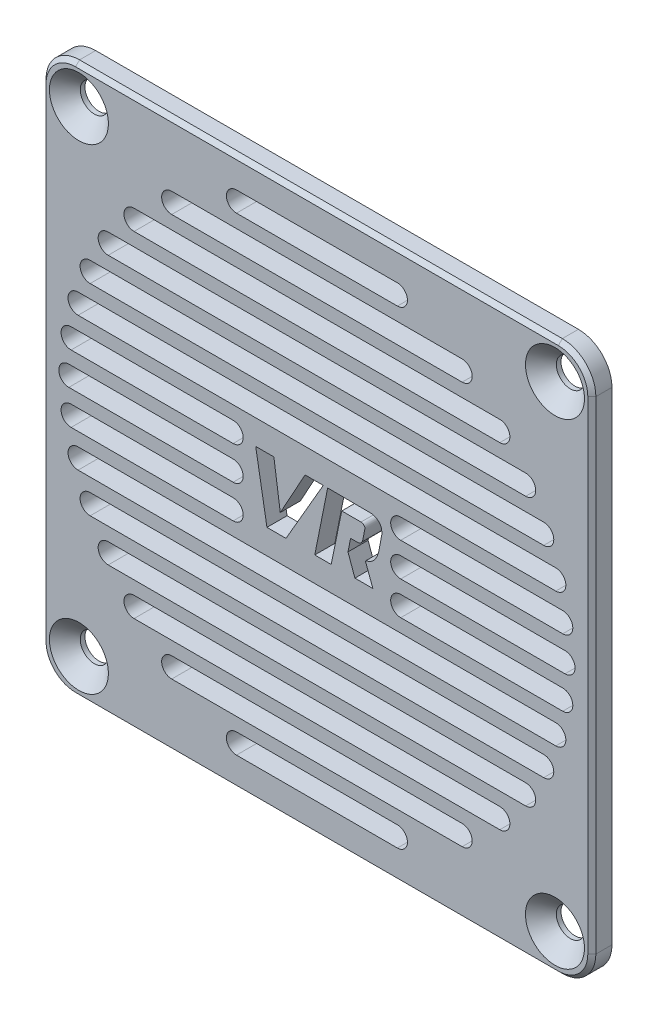
SolidWorks part; units mm, degrees
ref_plane "Front Plane" through (0, 0, 0) normal (0, 0, 1) x (1, 0, 0)
ref_plane "Top Plane" through (0, 0, 0) normal (0, 1, 0) x (1, 0, 0)
ref_plane "Right Plane" through (0, 0, 0) normal (1, 0, 0) x (0, 0, -1)
sketch "Sketch1" plane through (0, 0, 0) normal (0, 0, 1) x (1, 0, 0)
  line L0 (41, 36) -> (41, -36)
  line L1 (36, -41) -> (-36, -41)
  line L2 (-41, -36) -> (-41, 36)
  line L3 (-36, 41) -> (36, 41)
  line L4 (0, 6.288) -> (0, 0) construction
  line L5 (0, 0) -> (5.6688, 0) construction
  line L6 (102.5259, 3.6525) -> (240.1283, 3.6525) construction
  line L7 (237.3735, 205.8696) -> (682.0402, 205.8696) construction
  line L8 (155.5388, 233.4582) -> (600.2055, 233.4582) construction
  circle A0 centre (0, 0) radius 10.5 construction
  circle A3 centre (35.5, -35.5) radius 2.1
  circle A4 centre (-35.5, -35.5) radius 2.1
  circle A5 centre (-35.5, 35.5) radius 2.1
  circle A6 centre (35.5, 35.5) radius 2.1
  arc A7 (41, 36) -> (36, 41) centre (36, 36) ccw
  arc A8 (36, -41) -> (41, -36) centre (36, -36) ccw
  arc A9 (-41, -36) -> (-36, -41) centre (-36, -36) ccw
  arc A10 (-36, 41) -> (-41, 36) centre (-36, 36) ccw
  circle A11 centre (0, 0) radius 19.5 construction
  dimension "D1" = 39
  dimension "D2" = 21
  dimension "D5" = 5
  dimension "D6" = 4.2
  dimension "D3" = 82
  dimension "D4" = 82
  dimension "D7" = 71
  dimension "D8" = 71
extrude "Base" add sketch "Sketch1" along normal blind 3 contours L3 A10 L2 A9 L1 A8 L0 A7 A3 A4 A5 A6 region at (0, 0, 0)
chamfer "Chamfer1" distance 2.3 angle 45 4 edges at (37.6, -35.5, 3) (-33.4, -35.5, 3) (37.6, 35.5, 3) (-33.4, 35.5, 3)
sketch "Sketch3" plane through (0, 0, 3) normal (0, 0, 1) x (1, 0, 0)
  circle A0 centre (0, 0) radius 10.5 construction
  line B0 (0.9438, 4.8073) -> (-1.7703, 4.8073)
  line B1 (3.7035, 2.8898) -> (6.5735, 2.8898)
  line B2 (6.5735, 2.8898) -> (6.8393, 2.8463) construction
  line B3 (6.8393, 2.8463) -> (7.0318, 2.6813) construction
  line B4 (7.0318, 2.6813) -> (7.1365, 2.5072) construction
  line B5 (7.1365, 2.5072) -> (7.1365, 2.2404) construction
  line B6 (5.021, 0.0136) -> (6.1671, 0.0136)
  line B7 (6.1671, 0.0136) -> (6.4334, 0.0999) construction
  line B8 (6.4334, 0.0999) -> (6.6026, 0.2489) construction
  line B9 (6.6026, 0.2489) -> (6.7446, 0.4146) construction
  line B10 (6.7446, 0.4146) -> (6.8393, 0.6984) construction
  line B11 (6.8393, 0.6984) -> (7.1365, 2.2404) construction
  line B12 (4.6314, -1.9349) -> (5.021, 0.0136)
  line B13 (-9.1314, 4.8073) -> (-6.4211, 4.8073)
  line B14 (-6.4211, 4.8073) -> (-5.4671, -1.8998)
  line B15 (-5.4671, -1.8998) -> (-1.7703, 4.8073)
  line B16 (0.9438, 4.8073) -> (-4.6161, -4.8111)
  line B17 (-4.6161, -4.8111) -> (-7.4548, -4.8111)
  line B18 (-7.4548, -4.8111) -> (-9.1314, 4.8073)
  line B19 (1.6005, 4.8073) -> (8.0334, 4.7764)
  line B20 (7.2293, -1.8111) -> (8.3427, -4.8111)
  line B21 (8.3427, -4.8111) -> (5.6631, -4.8111)
  line B22 (5.6631, -4.8111) -> (4.6314, -1.9349)
  line B23 (3.7035, 2.8898) -> (2.1262, -4.8111)
  line B24 (2.1262, -4.8111) -> (-0.3232, -4.8111)
  line B25 (-0.3232, -4.8111) -> (1.6005, 4.8073)
  line B26 (9.6784, 2.8463) -> (9.2292, 0.4146)
  spline B27 degree 3 poles (9.2292, 0.4146) (9.1202, 0.0172) (8.9153, -0.5548) (8.4464, -1.1602) (7.9426, -1.5631) (7.4993, -1.705) (7.2293, -1.8111) knots 0 0 0 0 0.394089 0.566272 0.722136 1 1 1 1
  spline B28 degree 3 poles (9.6784, 2.8463) (9.687, 2.9892) (9.6873, 3.2192) (9.6341, 3.5736) (9.531, 3.877) (9.319, 4.175) (9.0589, 4.4168) (8.7482, 4.6112) (8.4048, 4.733) (8.1636, 4.7706) (8.0334, 4.7764) knots 0 0 0 0 0.150298 0.240096 0.375313 0.481557 0.62039 0.745312 0.863341 1 1 1 1
  spline B29 degree 3 poles (6.5735, 2.8898) (6.6399, 2.879) (6.7064, 2.8681) (6.7728, 2.8572) (6.7866, 2.8549) (6.8142, 2.8504) (6.8556, 2.8324) (6.8768, 2.8142) (6.8874, 2.8051) (6.9195, 2.7776) (6.9516, 2.7501) (6.9837, 2.7226) (6.9932, 2.7144) (7.0122, 2.6981) (7.0386, 2.67) (7.0515, 2.6485) (7.058, 2.6378) (7.0754, 2.6088) (7.0929, 2.5797) (7.1103, 2.5507) (7.1168, 2.5399) (7.1298, 2.5183) (7.1365, 2.4782) (7.1365, 2.453) (7.1365, 2.4405) (7.1365, 2.396) (7.1365, 2.3515) (7.1365, 2.3071) (7.1365, 2.2923) (7.1365, 2.2628) (7.1322, 2.2183) (7.1266, 2.1894) (7.1239, 2.1749) (7.0337, 1.7072) (6.9436, 1.2395) (6.8534, 0.7718) (6.8503, 0.7555) (6.844, 0.723) (6.8314, 0.6746) (6.8209, 0.6432) (6.8156, 0.6274) (6.7998, 0.5801) (6.784, 0.5328) (6.7683, 0.4855) (6.7638, 0.4721) (6.7549, 0.4454) (6.7366, 0.4053) (6.7183, 0.3838) (6.7091, 0.3731) (6.6854, 0.3455) (6.6617, 0.3179) (6.6381, 0.2903) (6.6301, 0.2809) (6.6141, 0.2623) (6.5879, 0.236) (6.5695, 0.2197) (6.5603, 0.2116) (6.5321, 0.1868) (6.5039, 0.1619) (6.4757, 0.1371) (6.4653, 0.128) (6.4447, 0.1099) (6.406, 0.091) (6.3799, 0.0825) (6.3668, 0.0783) (6.3002, 0.0567) (6.2336, 0.0352) (6.1671, 0.0136) knots 0 0 0 0 0.056598 0.056598 0.056598 0.068353 0.080109 0.091864 0.091864 0.091864 0.127378 0.127378 0.127378 0.137906 0.148433 0.158961 0.158961 0.158961 0.187427 0.187427 0.187427 0.198008 0.208589 0.21917 0.21917 0.21917 0.256543 0.256543 0.256543 0.268944 0.281346 0.293747 0.293747 0.293747 0.694048 0.694048 0.694048 0.707988 0.721929 0.735869 0.735869 0.735869 0.777781 0.777781 0.777781 0.789642 0.801504 0.813365 0.813365 0.813365 0.843938 0.843938 0.843938 0.854271 0.864604 0.874936 0.874936 0.874936 0.906514 0.906514 0.906514 0.91807 0.929625 0.941181 0.941181 0.941181 1 1 1 1
  dimension "D1" = 21
sketch_block_instance "Block1-1"
sketch_block "Block1" parameters "D1"=1.6237
extrude "Logo" cut sketch "Sketch3" against normal through all
sketch "Sketch4" plane through (0, 0, 3) normal (0, 0, 1) x (1, 0, 0)
  line L0 (-33.8231, 15) -> (33.8231, 15) construction
  line L1 (11, -5.7242) -> (-11, -5.7242) construction
  line L2 (0, 0) -> (-7.3146, 0) construction
  line L3 (11, -5.7242) -> (11, 5.7242) construction
  line L4 (11, 5.7242) -> (-11, 5.7242) construction
  line L5 (-11, -5.7242) -> (-11, 5.7242) construction
  line L6 (11, -5.7242) -> (-11, 5.7242) construction
  line L7 (11, 5.7242) -> (-11, -5.7242) construction
  line L8 (-33.8231, 16.5) -> (33.8231, 16.5)
  line L9 (-33.8231, 13.5) -> (33.8231, 13.5)
  line L10 (-35.623, 10) -> (35.623, 10) construction
  line L11 (-35.623, 11.5) -> (35.623, 11.5)
  line L12 (-35.623, 8.5) -> (35.623, 8.5)
  line L13 (-33.8231, -15) -> (33.8231, -15) construction
  line L14 (-33.8231, -13.5) -> (33.8231, -13.5)
  line L15 (-33.8231, -16.5) -> (33.8231, -16.5)
  line L16 (-35.623, -10) -> (35.623, -10) construction
  line L17 (-35.623, -8.5) -> (35.623, -8.5)
  line L18 (-35.623, -11.5) -> (35.623, -11.5)
  line L19 (12.5, 5) -> (36.6606, 5) construction
  line L20 (12.5, 6.5) -> (36.6606, 6.5)
  line L21 (12.5, 3.5) -> (36.6606, 3.5)
  line L22 (12.5, -5) -> (36.6606, -5) construction
  line L23 (12.5, -3.5) -> (36.6606, -3.5)
  line L24 (12.5, -6.5) -> (36.6606, -6.5)
  line L25 (-36.6606, 5) -> (-12.5, 5) construction
  line L26 (-36.6606, 6.5) -> (-12.5, 6.5)
  line L27 (-36.6606, 3.5) -> (-12.5, 3.5)
  line L28 (-36.6606, -5) -> (-12.5, -5) construction
  line L29 (-36.6606, -3.5) -> (-12.5, -3.5)
  line L30 (-36.6606, -6.5) -> (-12.5, -6.5)
  line L31 (0, 0) -> (0, 7.3736) construction
  line L32 (-37, 0) -> (-12.5, 0) construction
  line L33 (-37, 1.5) -> (-12.5, 1.5)
  line L34 (-37, -1.5) -> (-12.5, -1.5)
  line L35 (12.5, 0) -> (37, 0) construction
  line L36 (12.5, 1.5) -> (37, 1.5)
  line L37 (12.5, -1.5) -> (37, -1.5)
  line L38 (-31.1288, 20) -> (31.1288, 20) construction
  line L39 (-31.1288, 21.5) -> (31.1288, 21.5)
  line L40 (-31.1288, 18.5) -> (31.1288, 18.5)
  line L41 (-27.2764, 25) -> (27.2764, 25) construction
  line L42 (-27.2764, 26.5) -> (27.2764, 26.5)
  line L43 (-27.2764, 23.5) -> (27.2764, 23.5)
  line L44 (-21.6564, 30) -> (21.6564, 30) construction
  line L45 (-21.6564, 31.5) -> (21.6564, 31.5)
  line L46 (-21.6564, 28.5) -> (21.6564, 28.5)
  line L47 (-12, 35) -> (12, 35) construction
  line L48 (-12, 36.5) -> (12, 36.5)
  line L49 (-12, 33.5) -> (12, 33.5)
  line L50 (-31.1288, -20) -> (31.1288, -20) construction
  line L51 (-31.1288, -21.5) -> (31.1288, -21.5)
  line L52 (-31.1288, -18.5) -> (31.1288, -18.5)
  line L53 (-27.2764, -25) -> (27.2764, -25) construction
  line L54 (-27.2764, -26.5) -> (27.2764, -26.5)
  line L55 (-27.2764, -23.5) -> (27.2764, -23.5)
  line L56 (-21.6564, -30) -> (21.6564, -30) construction
  line L57 (-21.6564, -31.5) -> (21.6564, -31.5)
  line L58 (-21.6564, -28.5) -> (21.6564, -28.5)
  line L59 (-12, -35) -> (12, -35) construction
  line L60 (-12, -36.5) -> (12, -36.5)
  line L61 (-12, -33.5) -> (12, -33.5)
  circle A0 centre (0, 0) radius 38.5 construction
  circle A1 centre (0, 0) radius 10.5 construction
  arc A2 (-33.8231, 16.5) -> (-33.8231, 13.5) centre (-33.8231, 15) ccw
  arc A3 (33.8231, 13.5) -> (33.8231, 16.5) centre (33.8231, 15) ccw
  arc A4 (-35.623, 11.5) -> (-35.623, 8.5) centre (-35.623, 10) ccw
  arc A5 (35.623, 8.5) -> (35.623, 11.5) centre (35.623, 10) ccw
  arc A6 (-33.8231, -13.5) -> (-33.8231, -16.5) centre (-33.8231, -15) ccw
  arc A7 (33.8231, -16.5) -> (33.8231, -13.5) centre (33.8231, -15) ccw
  arc A8 (-35.623, -8.5) -> (-35.623, -11.5) centre (-35.623, -10) ccw
  arc A9 (35.623, -11.5) -> (35.623, -8.5) centre (35.623, -10) ccw
  arc A10 (12.5, 6.5) -> (12.5, 3.5) centre (12.5, 5) ccw
  arc A11 (36.6606, 3.5) -> (36.6606, 6.5) centre (36.6606, 5) ccw
  arc A12 (12.5, -3.5) -> (12.5, -6.5) centre (12.5, -5) ccw
  arc A13 (36.6606, -6.5) -> (36.6606, -3.5) centre (36.6606, -5) ccw
  arc A14 (-36.6606, 6.5) -> (-36.6606, 3.5) centre (-36.6606, 5) ccw
  arc A15 (-12.5, 3.5) -> (-12.5, 6.5) centre (-12.5, 5) ccw
  arc A16 (-36.6606, -3.5) -> (-36.6606, -6.5) centre (-36.6606, -5) ccw
  arc A17 (-12.5, -6.5) -> (-12.5, -3.5) centre (-12.5, -5) ccw
  arc A18 (-37, 1.5) -> (-37, -1.5) centre (-37, 0) ccw
  arc A19 (-12.5, -1.5) -> (-12.5, 1.5) centre (-12.5, 0) ccw
  arc A20 (12.5, 1.5) -> (12.5, -1.5) centre (12.5, 0) ccw
  arc A21 (37, -1.5) -> (37, 1.5) centre (37, 0) ccw
  arc A22 (-31.1288, 21.5) -> (-31.1288, 18.5) centre (-31.1288, 20) ccw
  arc A23 (31.1288, 18.5) -> (31.1288, 21.5) centre (31.1288, 20) ccw
  arc A24 (-27.2764, 26.5) -> (-27.2764, 23.5) centre (-27.2764, 25) ccw
  arc A25 (27.2764, 23.5) -> (27.2764, 26.5) centre (27.2764, 25) ccw
  arc A26 (-21.6564, 31.5) -> (-21.6564, 28.5) centre (-21.6564, 30) ccw
  arc A27 (21.6564, 28.5) -> (21.6564, 31.5) centre (21.6564, 30) ccw
  arc A28 (-12, 36.5) -> (-12, 33.5) centre (-12, 35) ccw
  arc A29 (12, 33.5) -> (12, 36.5) centre (12, 35) ccw
  arc A30 (-31.1288, -21.5) -> (-31.1288, -18.5) centre (-31.1288, -20) cw
  arc A31 (31.1288, -18.5) -> (31.1288, -21.5) centre (31.1288, -20) cw
  arc A32 (-27.2764, -26.5) -> (-27.2764, -23.5) centre (-27.2764, -25) cw
  arc A33 (27.2764, -23.5) -> (27.2764, -26.5) centre (27.2764, -25) cw
  arc A34 (-21.6564, -31.5) -> (-21.6564, -28.5) centre (-21.6564, -30) cw
  arc A35 (21.6564, -28.5) -> (21.6564, -31.5) centre (21.6564, -30) cw
  arc A36 (-12, -36.5) -> (-12, -33.5) centre (-12, -35) cw
  arc A37 (12, -33.5) -> (12, -36.5) centre (12, -35) cw
  point P6 (0, 15)
  point P16 (0, 10)
  point P23 (0, -15)
  point P30 (0, -10)
  point P37 (24.5803, 5)
  point P44 (24.5803, -5)
  point P51 (-24.5803, 5)
  point P58 (-24.5803, -5)
  point P68 (0, 20)
  point P71 (-24.75, 0)
  point P78 (24.75, 0)
  point P89 (0, 25)
  point P96 (0, 30)
  point P103 (0, 35)
  point P114 (0, -20)
  point P121 (0, -25)
  point P128 (0, -30)
  point P135 (0, -35)
  point P155 (0, 0)
  dimension "D1" = 77
  dimension "D2" = 21
  dimension "D4" = 3
  dimension "D5" = 3
  dimension "D3" = 22
  dimension "D6" = 3
  dimension "D7" = 3
  dimension "D8" = 3
  dimension "D9" = 3
  dimension "D10" = 2
  dimension "D11" = 2
  dimension "D12" = 2
  dimension "D13" = 2
  dimension "D14" = 2
  dimension "D15" = 2
  dimension "D16" = 2
  dimension "D17" = 2
extrude "Holes" cut sketch "Sketch4" against normal through all contours L9 A3 L8 A2 | L12 A5 L11 A4 | L27 A15 L26 A14 | L30 A17 L29 A16 | L18 A9 L17 A8 | L15 A7 L14 A6 | L24 A13 L23 A12 | L21 A11 L20 A10 | L34 A19 L33 A18 | L37 A21 L36 A20 | L40 A23 L39 A22 | L43 A25 L42 A24 | L46 A27 L45 A26 | L49 A29 L48 A28 | A31 L52 A30 L51 | A33 L55 A32 L54 | A35 L58 A34 L57 | A37 L61 A36 L60
chamfer "Chamfer2" distance 0.6 angle 45 8 edges at (0, -41, 3) (-39.5355, -39.5355, 3) (39.5355, -39.5355, 3) (-41, 0, 3) (41, 0, 3) (-39.5355, 39.5355, 3) (39.5355, 39.5355, 3) (0, 41, 3)
equation "\"D4\"=80"
equation "\"D3@Sketch1\"=\"D4@Sketch1\""
